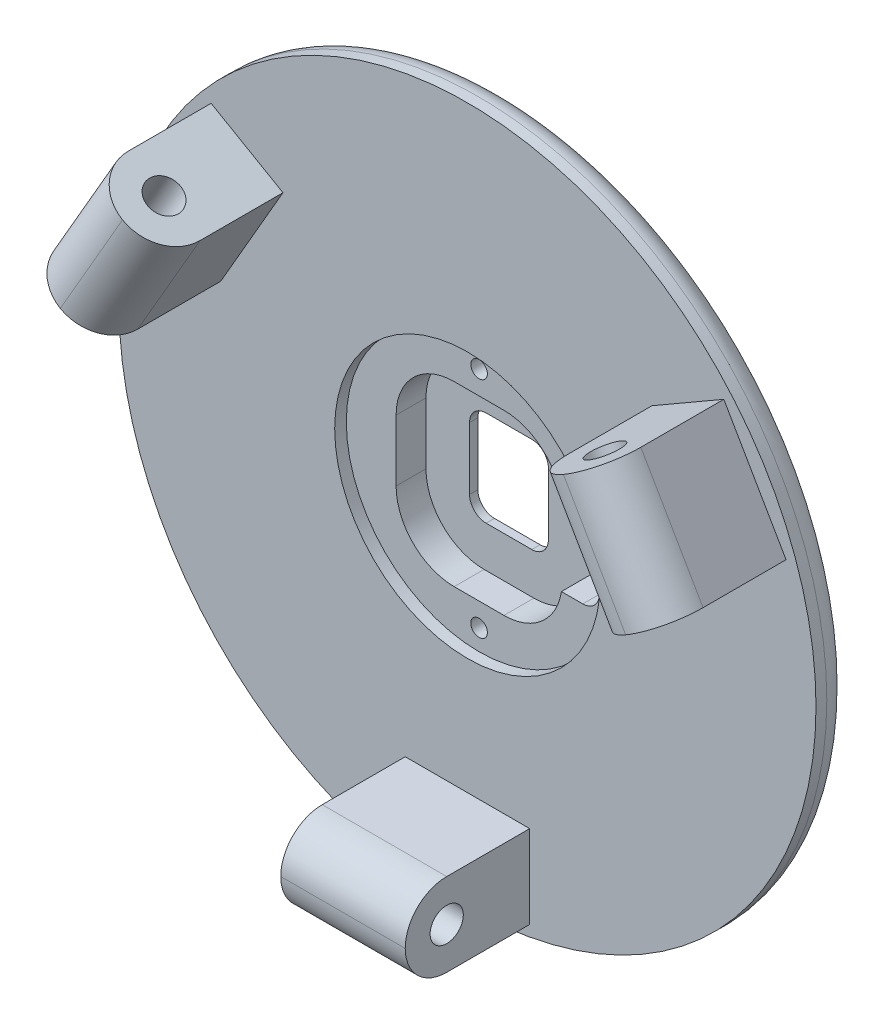
SolidWorks part; units mm, degrees
ref_plane "Front Plane" through (0, 0, 0) normal (0, 0, 1) x (1, 0, 0)
ref_plane "Top Plane" through (0, 0, 0) normal (0, 1, 0) x (1, 0, 0)
ref_plane "Right Plane" through (0, 0, 0) normal (1, 0, 0) x (0, 0, -1)
sketch "Sketch1" plane through (0, 0, 0) normal (0, 0, 1) x (1, 0, 0)
  line L0 (-11.547, 20) -> (-5.6345, 30.2407)
  line L1 (23.094, 0) -> (5.7735, 30)
  line L3 (-11.547, 20) -> (-28.8675, -10)
  line L5 (-11.547, -20) -> (23.094, -20)
  line L7 (5.7735, 30) -> (5.6345, 30.2407)
  line L8 (5.6345, 30.2407) -> (-5.6345, 30.2407)
  line L9 (23.094, 0) -> (29.0065, -10.2407)
  line L10 (23.372, -20) -> (29.0065, -10.2407)
  line L11 (23.094, -20) -> (23.372, -20)
  line L12 (-11.547, -20) -> (-23.372, -20)
  line L13 (-29.0065, -10.2407) -> (-23.372, -20)
  line L14 (-28.8675, -10) -> (-29.0065, -10.2407)
  line L15 (28.2843, 20) -> (10.9638, 20) [skipped]
  line L16 (-17.3205, -10) -> (-8.6603, -25) [skipped]
  line L17 (17.3205, -10) -> (25.9808, 5) [skipped]
  circle A0 centre (0, 0) radius 20 construction
  point P21 (0, 0)
  dimension "D1" = 40
  dimension "D2" = 3
extrude "Boss-Extrude1" add sketch "Sketch1" along normal blind 6
sketch "Sketch3" plane through (0, 0, 6) normal (0, 0, 1) x (1, 0, 0)
  circle A0 centre (0, 0) radius 3
  dimension "D1" = 6
extrude "Cut-Extrude1" cut sketch "Sketch3" against normal through all
sketch "Sketch8" plane through (0, 0, 6) normal (0, 0, 1) x (1, 0, 0)
  line L1 (-10, 10.7) -> (10, 10.7)
  line L2 (-10, 10.7) -> (-10, -10.7)
  line L3 (-10, -10.7) -> (10, -10.7)
  line L4 (10, 10.7) -> (10, -10.7)
  line L5 (-10, 10.7) -> (10, -10.7) construction
  line L6 (-10, -10.7) -> (10, 10.7) construction
  point P0 (0, 0)
  dimension "D1" = 21.4
  dimension "D2" = 20
extrude "Cut-Extrude5" cut sketch "Sketch8" against normal blind 5
fillet "Fillet8" radius 7 4 edges at (-10, -10.7, 3.5) (10, -10.7, 3.5) (10, 10.7, 3.5) (-10, 10.7, 3.5)
sketch "Sketch9" plane through (0, 0, 6) normal (0, 0, 1) x (1, 0, 0)
  line L0 (0, 0) -> (0, 13.5) construction
  line L1 (0, 0) -> (5.4771, 0) construction
  circle A0 centre (0, 13.5) radius 1
  circle A1 centre (0, -13.5) radius 1
  dimension "D1" = 2
  dimension "D2" = 13.5
extrude "Cut-Extrude6" cut sketch "Sketch9" against normal through all
sketch "Sketch10" plane through (0, 0, 1) normal (0, 0, 1) x (1, 0, 0)
  line L1 (-4.75, -5.75) -> (4.75, -5.75)
  line L2 (-4.75, -5.75) -> (-4.75, 5.75)
  line L3 (-4.75, 5.75) -> (4.75, 5.75)
  line L4 (4.75, -5.75) -> (4.75, 5.75)
  line L5 (-4.75, -5.75) -> (4.75, 5.75) construction
  line L6 (-4.75, 5.75) -> (4.75, -5.75) construction
  point P0 (0, 0)
  dimension "D1" = 11.5
  dimension "D2" = 9.5
extrude "Cut-Extrude7" cut sketch "Sketch10" against normal through all
fillet "Fillet9" radius 2 4 edges at (-4.75, -5.75, 0.5) (4.75, -5.75, 0.5) (4.75, 5.75, 0.5) (-4.75, 5.75, 0.5)
sketch "Sketch11" plane through (0, 0, 6) normal (0, 0, 1) x (1, 0, 0)
  line L0 (0, 0) -> (11.75, 0) construction
  line L2 (9, 4.75) -> (14.5, 4.75)
  line L3 (9, 4.75) -> (9, -4.75)
  line L4 (9, -4.75) -> (14.5, -4.75)
  line L5 (14.5, 4.75) -> (14.5, -4.75)
  line L6 (9, 4.75) -> (14.5, -4.75) construction
  line L7 (9, -4.75) -> (14.5, 4.75) construction
  dimension "D1" = 5.5
  dimension "D2" = 9.5
  dimension "D3" = 9
extrude "Cut-Extrude8" cut sketch "Sketch11" against normal blind 5
fillet "Fillet10" radius 2 2 edges at (14.5, -4.75, 3.5) (14.5, 4.75, 3.5)
sketch "Sketch12" plane through (0, 0, 6) normal (0, 0, 1) x (1, 0, 0)
  circle A0 centre (0, 0) radius 16
  dimension "D1" = 32
extrude "Cut-Extrude9" cut sketch "Sketch12" against normal blind 1.4
sketch "Sketch13" plane through (0, 0, 0) normal (0, 0, -1) x (-1, 0, 0)
  circle A0 centre (0, 13.5) radius 2.5
  circle A1 centre (0, -13.5) radius 2.5
  dimension "D1" = 5
extrude "Cut-Extrude10" cut sketch "Sketch13" against normal blind 2.4
sketch "Sketch14" plane through (0, 0, 0) normal (0, 0, -1) x (-1, 0, 0)
  line L1 (19.5387, 0) -> (9.7694, 16.921)
  line L2 (9.7694, 16.921) -> (-9.7694, 16.921)
  line L3 (-9.7694, 16.921) -> (-19.5387, 0)
  line L4 (-19.5387, 0) -> (-9.7694, -16.921)
  line L5 (-9.7694, -16.921) -> (9.7694, -16.921)
  line L6 (9.7694, -16.921) -> (19.5387, 0)
  circle A0 centre (0, 0) radius 16.921 construction
  circle A1 centre (0, 0) radius 42
  dimension "D1" = 84
extrude "Boss-Extrude3" add sketch "Sketch14" against normal blind 6
chamfer "Chamfer1" distance 2.6 angle 70 1 edges at (-42, 0, 0) first distance on face at (-42, 0, 6)
fillet "Fillet12" radius 3 2 edges at (-34.8566, 0, 0) (-42, 0, 2.6)
sketch "Sketch15" plane through (0, 0, 6) normal (0, 0, 1) x (1, 0, 0)
  line L0 (-29.7308, 8.5048) -> (-22.2308, 21.4952)
  line L1 (7.5, -30) -> (-7.5, -30)
  line L2 (7.5, -30) -> (7.5, -40)
  line L3 (7.5, -40) -> (-7.5, -40)
  line L4 (-7.5, -30) -> (-7.5, -40)
  line L5 (7.5, -30) -> (-7.5, -40) construction
  line L6 (7.5, -40) -> (-7.5, -30) construction
  line L7 (-29.7308, 8.5048) -> (-38.391, 13.5048)
  line L8 (-38.391, 13.5048) -> (-30.891, 26.4952)
  line L9 (-22.2308, 21.4952) -> (-30.891, 26.4952)
  line L10 (-29.7308, 8.5048) -> (-30.891, 26.4952) construction
  line L11 (-38.391, 13.5048) -> (-22.2308, 21.4952) construction
  line L12 (22.2308, 21.4952) -> (29.7308, 8.5048)
  line L13 (22.2308, 21.4952) -> (30.891, 26.4952)
  line L14 (30.891, 26.4952) -> (38.391, 13.5048)
  line L15 (29.7308, 8.5048) -> (38.391, 13.5048)
  line L16 (22.2308, 21.4952) -> (38.391, 13.5048) construction
  line L17 (30.891, 26.4952) -> (29.7308, 8.5048) construction
  circle A0 centre (0, 0) radius 35 construction
  point P3 (0, -35)
  point P10 (-30.3109, 17.5)
  point P15 (30.3109, 17.5)
  point P20 (0, 0)
  dimension "D1" = 70
  dimension "D2" = 10
  dimension "D3" = 15
  dimension "D4" = 3
extrude "Boss-Extrude4" add sketch "Sketch15" along normal blind 15
sketch "Sketch16" plane through (-3.75, 6.4952, 0) normal (-0.5, 0.866, 0) x (0.866, 0.5, 0)
  line L0 (30, -21) -> (30, -6) construction
  line L1 (40, -21) -> (30, -21) construction
  circle A0 centre (35, -16) radius 2
  dimension "D1" = 4
  dimension "D2" = 5
  dimension "D3" = 5
extrude "Cut-Extrude11" cut sketch "Sketch16" against normal blind 15
sketch "Sketch17" plane through (7.5, 0, 0) normal (1, 0, 0) x (0, 0, -1)
  line L0 (-21, -40) -> (-21, -30) construction
  circle A0 centre (-16, -35) radius 2
  dimension "D1" = 5
  dimension "D2" = 4
extrude "Cut-Extrude12" cut sketch "Sketch17" against normal blind 15
sketch "Sketch18" plane through (3.75, 6.4952, 0) normal (0.5, 0.866, 0) x (0.866, -0.5, 0)
  line L0 (-30, -21) -> (-40, -21) construction
  circle A0 centre (-35, -16) radius 2
  dimension "D1" = 4
  dimension "D2" = 5
extrude "Cut-Extrude13" cut sketch "Sketch18" against normal blind 15
fillet "Fillet13" radius 5 6 edges at (0, -40, 21) (0, -30, 21) (-34.641, 20, 21) (-25.9808, 15, 21) (25.9808, 15, 21) (34.641, 20, 21)
